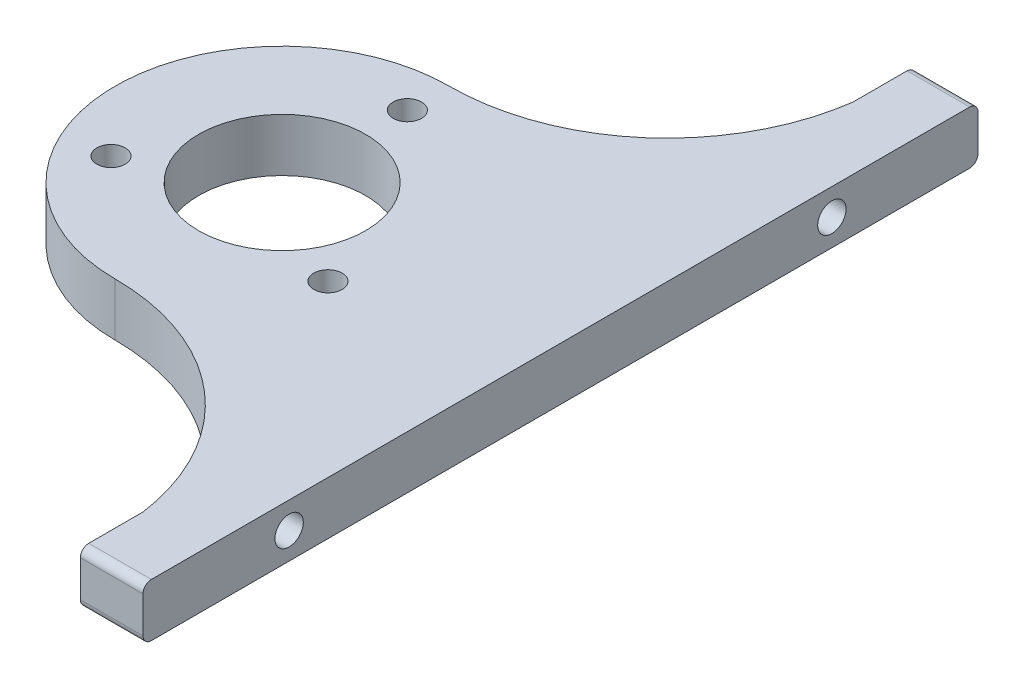
SolidWorks part; units mm, degrees
material "1060 Alloy"
ref_plane "Front Plane" through (0, 0, 0) normal (0, 0, 1) x (1, 0, 0)
ref_plane "Top Plane" through (0, 0, 0) normal (0, 1, 0) x (1, 0, 0)
ref_plane "Right Plane" through (0, 0, 0) normal (1, 0, 0) x (0, 0, -1)
sketch "Sketch1" plane through (0, 0, 0) normal (0, 1, 0) x (1, 0, 0)
  line L0 (33.34, 50) -> (33.34, -50)
  line L1 (0, 0) -> (94.428, 0) construction
  line L2 (33.34, 50) -> (25.84, 50)
  line L4 (33.34, -50) -> (25.84, -50)
  line L5 (25.84, 50) -> (25.84, 42.5)
  line L6 (25.84, -50) -> (25.84, -42.5)
  circle A0 centre (0, 0) radius 10
  arc A1 (0, 20) -> (0, -20) centre (0, 0) ccw
  arc A2 (0, 20) -> (25.84, 42.5) centre (0, 46.0879) ccw
  circle A3 centre (0, 0) radius 20 construction
  arc A4 (0, -20) -> (25.84, -42.5) centre (0, -46.0879) cw
  point P5 (19.1261, 5.8474)
  point P7 (0, 20)
  point P9 (0, -20)
  dimension "D1" = 20
  dimension "D3" = 100
  dimension "D4" = 50
  dimension "D5" = 7.5
  dimension "D6" = 7.5
  dimension "D7" = 7.5
  dimension "D8" = 7.5
  dimension "D2" = 10
extrude "Boss-Extrude1" add sketch "Sketch1" along normal blind 6.35
hole_wizard "M3 Clearance Hole1" positions "Sketch2" profile "Sketch3" hole size "M3" standard "ANSI Metric" end condition through all
sketch "Sketch2" plane through (0, 6.35, 0) normal (0, 1, 0) x (1, 0, 0)
  circle A0 centre (0, 0) radius 15 construction
  point P0 (0, 15)
  point P14 (12.9919, -7.4991)
  point P15 (-12.9889, -7.5009)
  point P16 (0.001, 0)
  dimension "D2" = 30
  dimension "D1" = 15
  dimension "D3" = 3
sketch "Sketch3" plane through (0, 6.35, -15) normal (1, 0, 0) x (0, 0, 1)
  line L0 (0, 0) -> (0, 6.35)
  line L1 (0, 6.35) -> (1.7, 6.35)
  line L2 (1.7, 6.35) -> (1.7, 0)
  line L5 (1.7, 0) -> (0, 0)
  line L11 (0, -6.35) -> (0, 107.95) construction
  dimension "Thru Hole Dia." = 3.4
  dimension "Thru Hole Depth" = 6.35
hole_wizard "M3 Clearance Hole3" positions "Sketch8" profile "Sketch9" hole size "M3" standard "ANSI Metric"
sketch "Sketch8" plane through (33.34, 0, 0) normal (1, 0, 0) x (0, 0, -1)
  line L0 (50, 3.175) -> (-50, 3.175) construction
  line L1 (50, 6.35) -> (50, 0) construction
  line L2 (-50, 6.35) -> (-50, 0) construction
  point P0 (32.5, 3.175)
  point P2 (-32.5, 3.175)
  dimension "D1" = 17.5
  dimension "D2" = 17.5
sketch "Sketch9" plane through (33.34, 3.175, -32.5) normal (0, 1, 0) x (0, 0, -1)
  line L0 (0, 0) -> (0, 8.0215)
  line L1 (0, 8.0215) -> (1.7, 7)
  line L2 (1.7, 7) -> (1.7, 0)
  line L5 (1.7, 0) -> (0, 0)
  line L10 (0, 8.0215) -> (-1.7, 7) construction
  line L11 (0, -6.35) -> (0, 107.95) construction
  dimension "Hole Dia." = 3.4
  dimension "Hole Depth" = 7
  dimension "Drill Angle" = 118
fillet "Fillet1" radius 1 4 edges at (29.59, 6.35, 50) (29.59, 0, 50) (29.59, 0, -50) (29.59, 6.35, -50)
